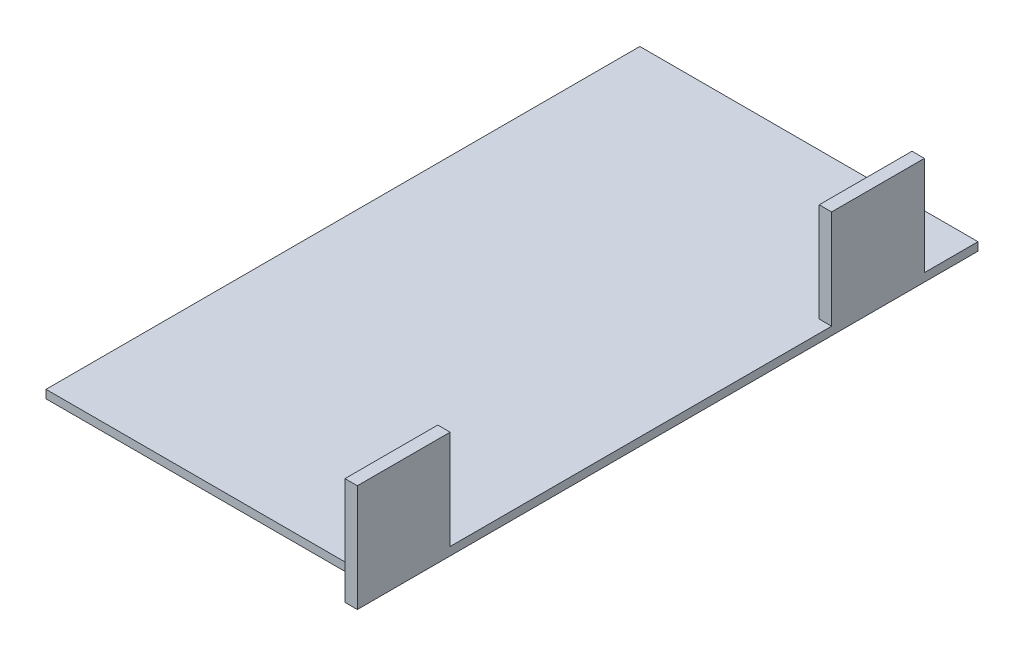
SolidWorks part; units mm, degrees
ref_plane "Alzado" through (0, 0, 0) normal (0, 0, 1) x (1, 0, 0)
ref_plane "Planta" through (0, 0, 0) normal (0, 1, 0) x (1, 0, 0)
ref_plane "Vista lateral" through (0, 0, 0) normal (1, 0, 0) x (0, 0, -1)
sketch "Croquis1" plane through (0, 0, 0) normal (0, 1, 0) x (1, 0, 0)
  line L1 (-41, 72) -> (41, 72)
  line L2 (-41, 72) -> (-41, -72)
  line L3 (-41, -72) -> (41, -72)
  line L4 (41, 72) -> (41, -72)
  line L5 (-41, 72) -> (41, -72) construction
  line L6 (-41, -72) -> (41, 72) construction
  point P0 (0, 0)
  dimension "D1" = 144
  dimension "D2" = 82
extrude "Saliente-Extruir1" add sketch "Croquis1" along normal blind 2
sketch "Croquis2" plane through (0, 0, 0) normal (0, -1, 0) x (1, 0, 0)
  line L0 (41, 72) -> (41, -72) construction
  line L1 (41, 56) -> (38, 56)
  line L2 (41, 56) -> (41, 78.5)
  line L3 (41, 78.5) -> (38, 78.5)
  line L4 (38, 56) -> (38, 78.5)
  line L5 (-41, 72) -> (41, 72) construction
  line L6 (41, -72) -> (-41, -72) construction
  line L7 (41, -59) -> (38, -59)
  line L8 (41, -59) -> (41, -36.5)
  line L9 (41, -36.5) -> (38, -36.5)
  line L10 (38, -59) -> (38, -36.5)
  dimension "D1" = 16
  dimension "D2" = 6.5
  dimension "D3" = 3
  dimension "D4" = 13
  dimension "D5" = 22.5
  dimension "D6" = 3
extrude "Saliente-Extruir4" add sketch "Croquis2" against normal blind 26
